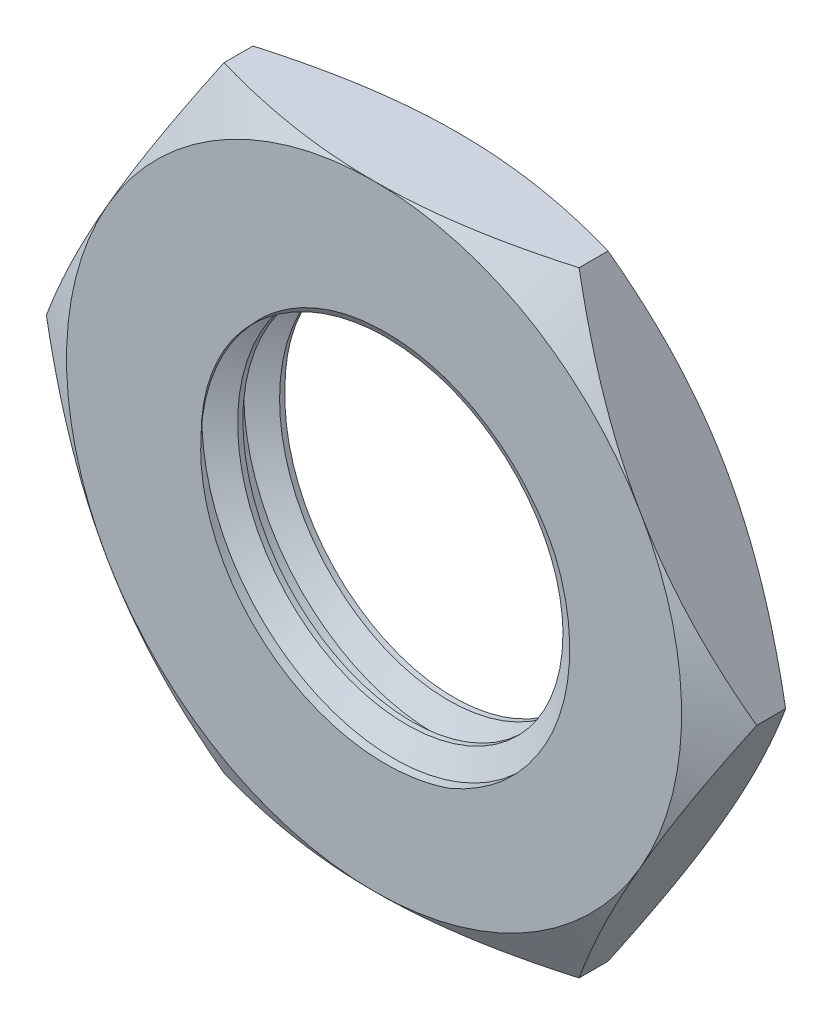
SolidWorks part; units mm, degrees
ref_plane "Plan de face" through (0, 0, 0) normal (0, 0, 1) x (1, 0, 0)
ref_plane "Plan de dessus" through (0, 0, 0) normal (0, 1, 0) x (1, 0, 0)
ref_plane "Plan de droite" through (0, 0, 0) normal (1, 0, 0) x (0, 0, -1)
sketch "Contour_écrou_M14" plane through (0, 0, 0) normal (0, 0, 1) x (1, 0, 0)
  line L1 (12.7017, 0) -> (6.3509, 11)
  line L2 (6.3509, 11) -> (-6.3509, 11)
  line L3 (-6.3509, 11) -> (-12.7017, 0)
  line L4 (-12.7017, 0) -> (-6.3509, -11)
  line L5 (-6.3509, -11) -> (6.3509, -11)
  line L6 (6.3509, -11) -> (12.7017, 0)
  circle A0 centre (0, 0) radius 11 construction
  dimension "D1" = 22
extrude "Boss.-Extru.1_Contour_écrou_M14" add sketch "Contour_écrou_M14" along normal mid plane 3
sketch "Tap_Drill_Hole" plane through (0, 0, -1.5) normal (0, 0, -1) x (-1, 0, 0)
  circle A0 centre (0, 0) radius 6.188
  dimension "D1" = 12.376
extrude "Enlèv. mat.-Extru.2_Tap_Drill_Hole" cut sketch "Tap_Drill_Hole" against normal up to next
ref_axis "Axe1_central" through (0, 0, -0.9656) along (0, 0, 1)
sketch "Coins ronds" plane through (0, 0, -1.5) normal (0, 0, -1) x (-1, 0, 0)
  line L0 (6.3509, 11) -> (12.7017, 0) construction
  circle A0 centre (0, 0) radius 11
extrude "Enlèv. mat.-Extru.1_Coins ronds" cut sketch "Coins ronds" against normal blind 10 draft 60 flip side to cut
mirror "Symétrie1_Coins ronds" about plane through (0, 0, 0) normal (0, 0, 1) of "Enlèv. mat.-Extru.1_Coins ronds"
sketch "Esquisse4" plane through (0, 0, -1.5) normal (0, 0, -1) x (-1, 0, 0)
  circle A0 centre (0, 0) radius 6.75
curve "Hélice/Spirale1" pitch 1.5 height 7.5 radius 6.75 centre (0, 0, -1.5) axis (0, 0, 1) start towards (-1, 0, 0)
sketch "Dents" plane through (0, 0, 0) normal (0, 1, 0) x (1, 0, 0)
  line L0 (-6.188, 2.8126) -> (-6.188, 1.5)
  line L1 (-6.188, 1.5) -> (-7, 1.9688)
  line L2 (-7.3248, 2.1563) -> (-7, 2.3438) construction
  line L3 (-6.188, 1.5) -> (-6.188, -1.5) construction
  line L4 (-7, 2.3438) -> (-7, 1.9688)
  line L5 (-7, 2.3438) -> (-6.188, 2.8126)
  line L6 (-7, 1.9688) -> (-7.3248, 2.1563) construction
  line L7 (0, 1.5) -> (-9.5263, 1.5) construction
  dimension "D1" = 60
  dimension "D2" = 0.812
  dimension "D3" = 0.375
sweep "Enlèvement de matière-Balayage1" cut profiles "Dents" path "Hélice/Spirale1" align with end faces yes
